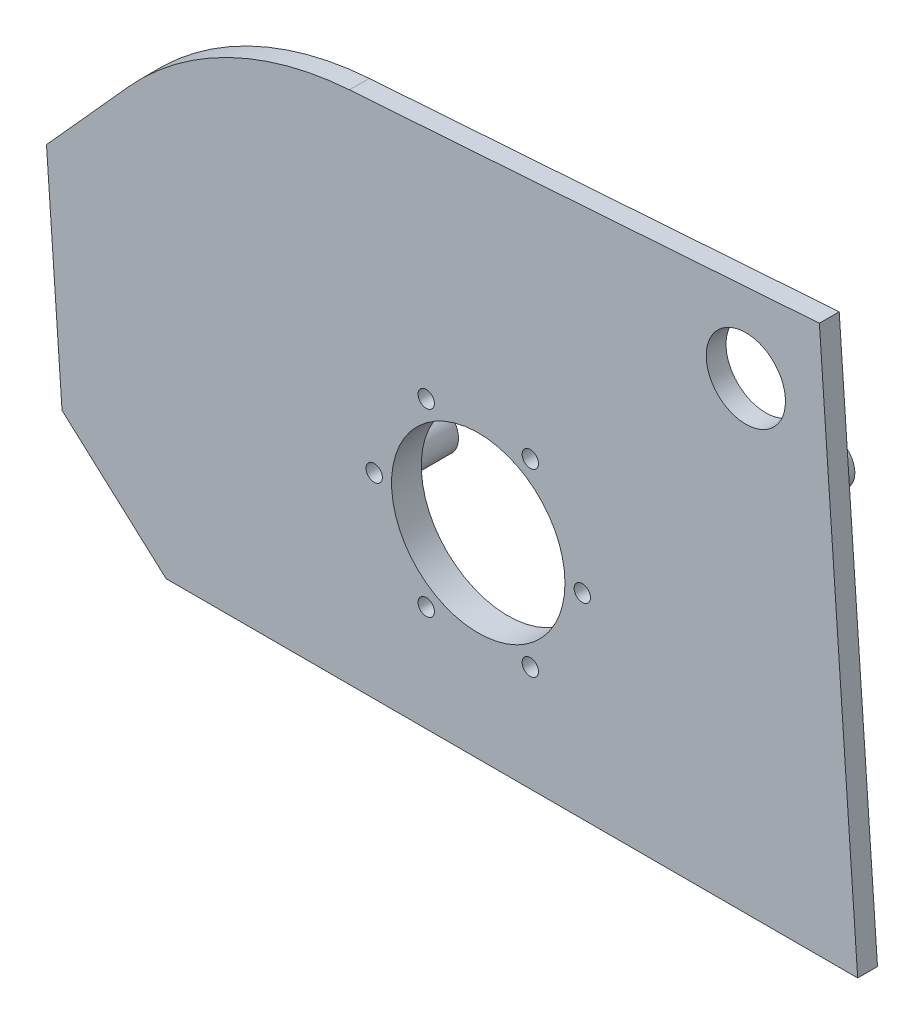
SolidWorks part; units mm, degrees
material "ABS"
ref_plane "Front Plane" through (0, 0, 0) normal (0, 0, 1) x (1, 0, 0)
ref_plane "Top Plane" through (0, 0, 0) normal (0, 1, 0) x (1, 0, 0)
ref_plane "Right Plane" through (0, 0, 0) normal (1, 0, 0) x (0, 0, -1)
sketch "Sketch2" plane through (0, 0, 0) normal (0, 0, 1) x (1, 0, 0)
  line L0 (-87.139, 24.2989) -> (-84, -20.5915)
  line L1 (-84, -20.5915) -> (-63, -39.5)
  line L2 (-63, -39.5) -> (76.5772, -39.5)
  line L3 (-26, 64.4449) -> (68.8449, 71.0771)
  line L5 (-87.139, 24.2989) -> (-70.5603, 42.7114)
  line L7 (76.5772, -39.5) -> (68.8449, 71.0771)
  line L8 (0, 0) -> (54, 54) construction
  line L10 (68.8449, 71.0771) -> (51.7206, 51.3779) construction
  line L11 (-47.6182, 0) -> (49.7288, 0) construction
  line L12 (-42.5, 13.2583) -> (-42.5, -13.2583)
  line L17 (-37.5, 13.2583) -> (-37.5, -13.2583)
  line L18 (-42.5, 13.2583) -> (-37.5, 13.2583) construction
  line L19 (0, -75.7784) -> (0, 71.0771) construction
  line L20 (42.5, 13.2583) -> (42.5, -13.2583)
  line L21 (37.5, 13.2583) -> (37.5, -13.2583)
  circle A0 centre (0, 0) radius 34.5 construction
  circle A1 centre (54, 54) radius 8
  circle A8 centre (0, 0) radius 16 construction
  circle A9 centre (0, 0) radius 17.5
  circle A10 centre (0, 0) radius 21 construction
  circle A11 centre (-10.5, 18.1865) radius 1.65
  arc A17 (-70.5603, 42.7114) -> (-26, 64.4449) centre (-21.384, -1.5672) cw
  arc A19 (-14.487, 17.8641) -> (-22.7143, 3.614) centre (0, 0) ccw
  arc A20 (-8.2273, 21.4782) -> (-14.487, 17.8641) centre (-10.5, 18.1865) ccw
  circle A21 centre (10.5, 18.1865) radius 1.65
  arc A22 (14.487, 17.8641) -> (8.2273, 21.4782) centre (10.5, 18.1865) ccw
  circle A23 centre (21, 0) radius 1.65
  arc A24 (22.7143, -3.614) -> (22.7143, 3.614) centre (21, 0) ccw
  circle A25 centre (10.5, -18.1865) radius 1.65
  arc A26 (8.2273, -21.4782) -> (14.487, -17.8641) centre (10.5, -18.1865) ccw
  circle A27 centre (-10.5, -18.1865) radius 1.65
  arc A28 (-14.487, -17.8641) -> (-8.2273, -21.4782) centre (-10.5, -18.1865) ccw
  circle A29 centre (-21, 0) radius 1.65
  arc A30 (-22.7143, 3.614) -> (-22.7143, -3.614) centre (-21, 0) ccw
  arc A31 (8.2273, 21.4782) -> (-8.2273, 21.4782) centre (0, 0) ccw
  arc A32 (22.7143, 3.614) -> (14.487, 17.8641) centre (0, 0) ccw
  arc A33 (14.487, -17.8641) -> (22.7143, -3.614) centre (0, 0) ccw
  arc A34 (-8.2273, -21.4782) -> (8.2273, -21.4782) centre (0, 0) ccw
  arc A35 (-22.7143, -3.614) -> (-14.487, -17.8641) centre (0, 0) ccw
  arc A36 (-37.5, 13.2583) -> (-42.5, 13.2583) centre (-40, 17) ccw
  circle A37 centre (-40, 17) radius 2.2
  circle A38 centre (-40, -17) radius 2.2
  arc A39 (-37.5, -13.2583) -> (-42.5, -13.2583) centre (-40, -17) cw
  circle A40 centre (40, 17) radius 2.2
  arc A41 (37.5, 13.2583) -> (42.5, 13.2583) centre (40, 17) cw
  circle A42 centre (40, -17) radius 2.2
  arc A43 (37.5, -13.2583) -> (42.5, -13.2583) centre (40, -17) ccw
  point P42 (0, 0)
  point P45 (0, 0)
  point P46 (-40, 13.2583)
  point P47 (-37.5, 0)
  point P56 (-42.5, 0)
  dimension "D1" = 69
  dimension "D3" = 6
  dimension "D4" = 5
  dimension "D5" = 54
  dimension "D6" = 45
  dimension "D7" = 16
  dimension "D8" = 8
  dimension "D26" = 32
  dimension "D27" = 1.5
  dimension "D28" = 42
  dimension "D29" = 3.3
  dimension "D9" = 2
  dimension "D10" = 86
  dimension "D11" = 42
  dimension "D12" = 21
  dimension "D13" = 45
  dimension "D14" = 84
  dimension "D15" = 26
  dimension "D16" = 8
  dimension "D17" = 34
  dimension "D18" = 5
  dimension "D19" = 3
  dimension "D20" = 9
  dimension "D21" = 4.4
  dimension "D22" = 35
extrude "Boss-Extrude2" add sketch "Sketch2" against normal blind 4 contours L7 L3 A17 L5 L0 L1 L2 A0 | A1 | A19 A30 A35 A28 A34 A26 A33 A24 A32 A22 A31 A20 | A9 | A39 L12 A36 L17 | A41 L20 A43 L21 region at (-77.3815, 32.1832, 0)
extrude "Boss-Extrude3" add sketch "Sketch2<3>" against normal blind 6 contours A30 A35 A28 A34 A26 A33 A24 A32 A22 A31 A20 A19 A9 A11 A21 A23 A25 A27 A29 | A21 | A25 | A23 | A11 | A27 | A29 region at (-12.1603, 21.0622, 0)
sketch "Sketch2<3>" plane through (0, 0, 0) normal (0, 0, 1) x (1, 0, 0) same geometry as "Sketch2"
extrude "Cut-Extrude1" cut sketch "Sketch2<6>" along direction (0, 0, 1) on the side against the normal through all contours A21 | A23 | A25 | A27 | A29 | A11
sketch "Sketch2<6>" plane through (0, 0, 0) normal (0, 0, 1) x (1, 0, 0) same geometry as "Sketch2"
extrude "Boss-Extrude4" add sketch "Sketch2<7>" against normal blind 31.5 contours L21 A43 L20 A41 | L12 A39 L17 A36
sketch "Sketch2<7>" plane through (0, 0, 0) normal (0, 0, 1) x (1, 0, 0) same geometry as "Sketch2"
extrude "Cut-Extrude2" cut sketch "Sketch2<8>" along normal blind 7 from surface contours A40 | A42 | A37 | A38 starting at face at (40, 0, -31.5)
sketch "Sketch2<8>" plane through (0, 0, 0) normal (0, 0, 1) x (1, 0, 0) same geometry as "Sketch2"
